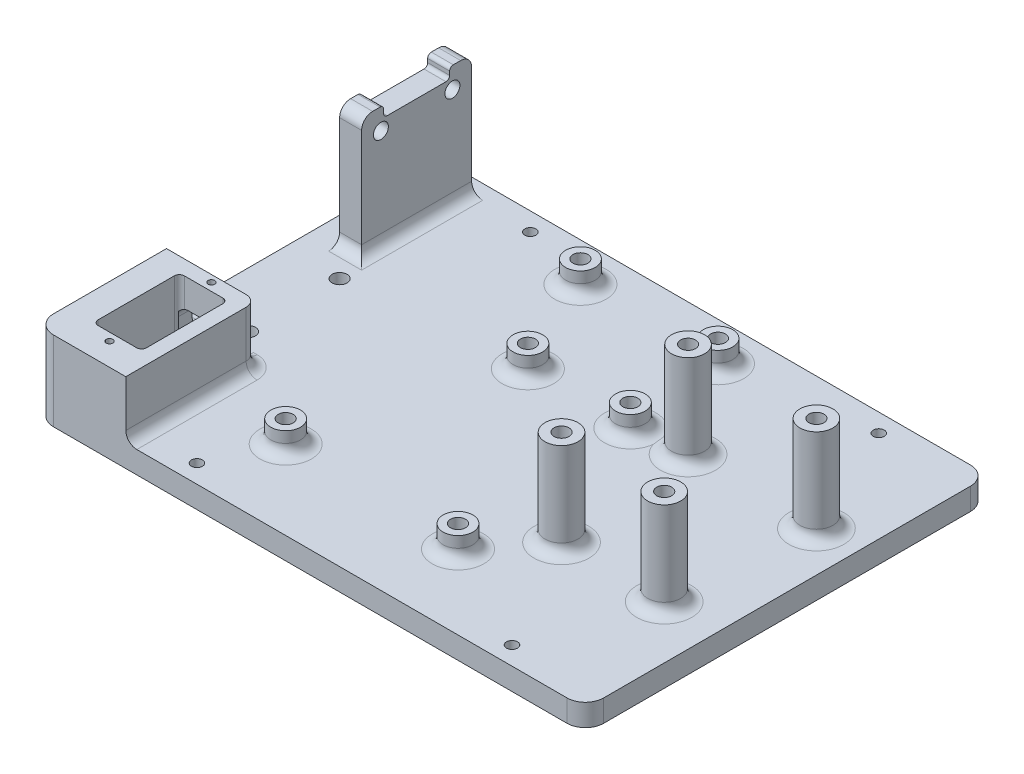
SolidWorks part; units mm, degrees
ref_plane "Front Plane" through (0, 0, 0) normal (0, 0, 1) x (1, 0, 0)
ref_plane "Top Plane" through (0, 0, 0) normal (0, 1, 0) x (1, 0, 0)
ref_plane "Right Plane" through (0, 0, 0) normal (1, 0, 0) x (0, 0, -1)
sketch "Sketch1" plane through (0, 0, 0) normal (0, 1, 0) x (1, 0, 0)
  line L1 (0, 0) -> (150, 0)
  line L2 (0, 0) -> (0, 110)
  line L3 (0, 110) -> (150, 110)
  line L4 (150, 0) -> (150, 110)
  dimension "D1" = 150
  dimension "D2" = 110
extrude "Boss-Extrude1" add sketch "Sketch1" along normal blind 6
hole_wizard "#8 (0.199) Diameter Hole1" positions "Sketch2" profile "Sketch3" hole size "#20" standard "ANSI Inch" end condition up to next
sketch "Sketch2" plane through (0, 6, 0) normal (0, 1, 0) x (1, 0, 0)
  point P0 (89.88, 72.39)
  point P3 (61.94, 72.39)
  point P6 (46.7, 21.59)
  point P9 (94.96, 20.32)
  point P24 (49.16, 99.5)
  point P27 (86.66, 99.5)
  point P30 (15, 68)
  point P33 (15, 43)
  point P36 (0, 0)
sketch "Sketch3" plane through (89.88, 6, -72.39) normal (1, 0, 0) x (0, 0, 1)
  line L0 (0, 0) -> (0, 6)
  line L1 (0, 6) -> (2.0447, 6)
  line L2 (2.0447, 6) -> (2.0447, 0)
  line L5 (2.0447, 0) -> (0, 0)
  line L11 (0, -6.35) -> (0, 107.95) construction
  dimension "Thru Hole Dia." = 4.0894
  dimension "Thru Hole Depth" = 6
sketch "Sketch4" plane through (0, 6, 0) normal (0, 1, 0) x (1, 0, 0)
  line L0 (150, 110) -> (0, 110) construction
  line L1 (7, 106) -> (13, 106)
  line L2 (7, 106) -> (7, 76)
  line L3 (7, 76) -> (13, 76)
  line L4 (13, 106) -> (13, 76)
  line L5 (0, 110) -> (0, 0) construction
  dimension "D1" = 30
  dimension "D2" = 6
  dimension "D3" = 4
  dimension "D4" = 7
extrude "Boss-Extrude2" add sketch "Sketch4" along normal blind 30
ref_plane "Plane1" through (0, 0, -91) normal (0, 0, -1) x (-1, 0, 0)
hole_wizard "#20 (0.161) Diameter Hole1" positions "Sketch5" profile "Sketch6" hole size "#20" standard "ANSI Inch" end condition up to next
sketch "Sketch5" plane through (7, 0, 0) normal (-1, 0, 0) x (0, 0, 1)
  point P0 (-81.25, 33.27)
  point P3 (-100.75, 33.27)
sketch "Sketch6" plane through (7, 33.27, -81.25) normal (0, 1, 0) x (0, 0, 1)
  line L0 (0, 0) -> (0, 6)
  line L1 (0, 6) -> (2.0447, 6)
  line L2 (2.0447, 6) -> (2.0447, 0)
  line L5 (2.0447, 0) -> (0, 0)
  line L11 (0, -6.35) -> (0, 107.95) construction
  dimension "Thru Hole Dia." = 4.0894
  dimension "Thru Hole Depth" = 6
sketch "Sketch7" plane through (0, 36, 0) normal (0, 1, 0) x (1, 0, 0)
  line L0 (13, 76) -> (13, 106) construction
  line L1 (7, 106) -> (13, 106)
  line L2 (7, 106) -> (7, 100)
  line L3 (7, 100) -> (13, 100)
  line L4 (13, 106) -> (13, 100)
  line L6 (7, 76) -> (13, 76)
  line L7 (7, 76) -> (7, 82)
  line L8 (7, 82) -> (13, 82)
  line L9 (13, 76) -> (13, 82)
  dimension "D1" = 6
  dimension "D2" = 6
extrude "Boss-Extrude3" add sketch "Sketch7" along normal blind 3
sketch "Sketch9" plane through (0, 6, 0) normal (0, 1, 0) x (1, 0, 0)
  line L0 (20.2, 9.65) -> (20.2, 30.45) construction
  line L1 (8.85, 8.8) -> (19.35, 8.8) construction
  line L2 (8, 30.45) -> (8, 9.65) construction
  line L3 (19.35, 31.3) -> (8.85, 31.3) construction
  line L4 (20.2, 9.65) -> (20.2, 30.45) construction
  line L5 (8.85, 8.8) -> (19.35, 8.8) construction
  line L6 (8, 30.45) -> (8, 9.65) construction
  line L7 (19.35, 31.3) -> (8.85, 31.3) construction
  line L8 (20.7, 9.65) -> (20.7, 30.45)
  line L9 (19.35, 31.8) -> (8.85, 31.8)
  line L10 (7.5, 30.45) -> (7.5, 9.65)
  line L11 (8.85, 8.3) -> (19.35, 8.3)
  line L13 (0, 0) -> (24.7, 0)
  line L14 (0, 0) -> (0, 35.8)
  line L15 (0, 35.8) -> (24.7, 35.8)
  line L16 (24.7, 0) -> (24.7, 35.8)
  arc A0 (20.2, 30.45) -> (19.35, 31.3) centre (19.35, 30.45) ccw construction
  arc A1 (19.35, 8.8) -> (20.2, 9.65) centre (19.35, 9.65) ccw construction
  arc A2 (8, 9.65) -> (8.85, 8.8) centre (8.85, 9.65) ccw construction
  arc A3 (8.85, 31.3) -> (8, 30.45) centre (8.85, 30.45) ccw construction
  arc A4 (20.2, 30.45) -> (19.35, 31.3) centre (19.35, 30.45) ccw construction
  arc A5 (19.35, 8.8) -> (20.2, 9.65) centre (19.35, 9.65) ccw construction
  arc A6 (8, 9.65) -> (8.85, 8.8) centre (8.85, 9.65) ccw construction
  arc A7 (8.85, 31.3) -> (8, 30.45) centre (8.85, 30.45) ccw construction
  arc A8 (20.7, 30.45) -> (19.35, 31.8) centre (19.35, 30.45) ccw
  arc A9 (8.85, 31.8) -> (7.5, 30.45) centre (8.85, 30.45) ccw
  arc A10 (7.5, 9.65) -> (8.85, 8.3) centre (8.85, 9.65) ccw
  arc A11 (19.35, 8.3) -> (20.7, 9.65) centre (19.35, 9.65) ccw
  dimension "D2" = 4
  dimension "D3" = 4
  dimension "D1" = 0.5
extrude "Boss-Extrude4" add sketch "Sketch9" along normal blind 15.7
sketch "Sketch10" plane through (0, 0, -35.8) normal (0, 0, -1) x (-1, 0, 0)
  line L0 (-7, 39) -> (-7, 6) construction
  line L1 (-20.7, 6) -> (-7, 6)
  line L2 (-20.7, 6) -> (-20.7, 14)
  line L3 (-20.7, 14) -> (-7, 14)
  line L4 (-7, 6) -> (-7, 14)
  dimension "D1" = 8
extrude "Cut-Extrude1" cut sketch "Sketch10" against normal up to surface (4.5 mm away)
sketch "Sketch11" plane through (0, 6, 0) normal (0, 1, 0) x (1, 0, 0)
  arc A0 (108.75, 36) -> (106.25, 36) centre (107.5, 36) ccw construction
  arc A1 (136.75, 36) -> (134.25, 36) centre (135.5, 36) ccw construction
  arc A2 (140.25, 74) -> (137.75, 74) centre (139, 74) ccw construction
  arc A3 (105.25, 74) -> (102.75, 74) centre (104, 74) ccw construction
  arc A4 (108.75, 36) -> (106.25, 36) centre (107.5, 36) ccw construction
  arc A5 (136.75, 36) -> (134.25, 36) centre (135.5, 36) ccw construction
  arc A6 (140.25, 74) -> (137.75, 74) centre (139, 74) ccw construction
  arc A7 (105.25, 74) -> (102.75, 74) centre (104, 74) ccw construction
  circle A8 centre (104, 74) radius 4.5
  circle A9 centre (139, 74) radius 4.5
  circle A10 centre (107.5, 36) radius 4.5
  circle A11 centre (135.5, 36) radius 4.5
  dimension "D1" = 9
extrude "Boss-Extrude5" add sketch "Sketch11" along normal blind 26
hole_wizard "#20 (0.161) Diameter Hole2" positions "Sketch12" profile "Sketch13" hole size "#20" standard "ANSI Inch" end condition up to next
sketch "Sketch12" plane through (0, 32, 0) normal (0, 1, 0) x (1, 0, 0)
  point P0 (104, 74)
  point P3 (139, 74)
  point P6 (107.5, 36)
  point P9 (135.5, 36)
sketch "Sketch13" plane through (104, 32, -74) normal (1, 0, 0) x (0, 0, 1)
  line L0 (0, 0) -> (0, 32)
  line L1 (0, 32) -> (2.0447, 32)
  line L2 (2.0447, 32) -> (2.0447, 0)
  line L5 (2.0447, 0) -> (0, 0)
  line L11 (0, -6.35) -> (0, 107.95) construction
  dimension "Thru Hole Dia." = 4.0894
  dimension "Thru Hole Depth" = 32
fillet "Fillet3" radius 5 4 edges at (150, 3, -110) (150, 3, 0) (0, 10.85, 0) (0, 3, -110)
sketch "Sketch17" plane through (0, 6, 0) normal (0, 1, 0) x (1, 0, 0)
  circle A0 centre (94.96, 20.32) radius 2.0447 construction
  circle A1 centre (46.7, 21.59) radius 2.0447 construction
  circle A2 centre (89.88, 72.39) radius 2.0447 construction
  circle A3 centre (61.94, 72.39) radius 2.0447 construction
  circle A4 centre (86.66, 99.5) radius 2.0447 construction
  circle A5 centre (49.16, 99.5) radius 2.0447 construction
  circle A6 centre (94.96, 20.32) radius 2.0447
  circle A7 centre (46.7, 21.59) radius 2.0447
  circle A8 centre (89.88, 72.39) radius 2.0447
  circle A9 centre (61.94, 72.39) radius 2.0447
  circle A10 centre (86.66, 99.5) radius 2.0447
  circle A11 centre (49.16, 99.5) radius 2.0447
  circle A12 centre (49.16, 99.5) radius 4.0447
  circle A13 centre (86.66, 99.5) radius 4.0447
  circle A14 centre (61.94, 72.39) radius 4.0447
  circle A15 centre (89.88, 72.39) radius 4.0447
  circle A16 centre (46.7, 21.59) radius 4.0447
  circle A17 centre (94.96, 20.32) radius 4.0447
  dimension "D1" = 2
extrude "Boss-Extrude6" add sketch "Sketch17" along normal blind 6
fillet "Fillet4" radius 3 20 edges at (107.5, 6, -40.5) (10, 39, -76) (10, 39, -106) (10, 6, -76) (13, 6, -91) (20.7, 14, -33.55) (7, 14, -33.55) (24.7, 13.85, -35.8) (22.7, 6, -35.8) (3.5, 6, -35.8) (24.7, 6, -17.9) (104, 6, -78.5) (139, 6, -78.5) (135.5, 6, -40.5) (49.16, 6, -103.5447) (86.66, 6, -103.5447) (61.94, 6, -76.4347) (89.88, 6, -76.4347) (94.96, 6, -24.3647) (46.7, 6, -25.6347)
fillet "Fillet5" radius 1 4 edges at (10, 36, -100) (10, 39, -100) (10, 39, -82) (10, 36, -82)
hole_wizard "Ø3.0mm Dowel Hole1" positions "Sketch14" profile "Sketch15" hole size "Ø3.0" standard "ANSI Metric" end condition up to next
sketch "Sketch14" plane through (0, 6, 0) normal (0, 1, 0) x (1, 0, 0)
  line L0 (145, 110) -> (5, 110) construction
  line L1 (150, 5) -> (150, 105) construction
  line L3 (27.7, 0) -> (145, 0) construction
  line L4 (0, 105) -> (0, 38.8) construction
  line L6 (34.1, 0) -> (34.1, 40.2) construction
  point P0 (30, 105)
  point P2 (39.1, 5)
  point P4 (125, 5)
  point P6 (125, 105)
  dimension "D1" = 5
  dimension "D2" = 25
  dimension "D3" = 5
  dimension "D4" = 5
  dimension "D5" = 30
sketch "Sketch15" plane through (30, 6, -105) normal (1, 0, 0) x (0, 0, 1)
  line L0 (0, 0) -> (0, 6)
  line L1 (0, 6) -> (1.5, 6)
  line L2 (1.5, 6) -> (1.5, 0)
  line L5 (1.5, 0) -> (0, 0)
  line L11 (0, -6.35) -> (0, 107.95) construction
  dimension "Thru Hole Dia." = 3
  dimension "Thru Hole Depth" = 6
sketch "Sketch16" plane through (0, 21.7, 0) normal (0, 1, 0) x (1, 0, 0)
  circle A0 centre (14.1, 6.15) radius 0.9
  circle A1 centre (14.1, 33.95) radius 0.9
  dimension "D1" = 1.8
  dimension "D2" = 1.8
extrude "Cut-Extrude2" cut sketch "Sketch16" against normal blind 5
